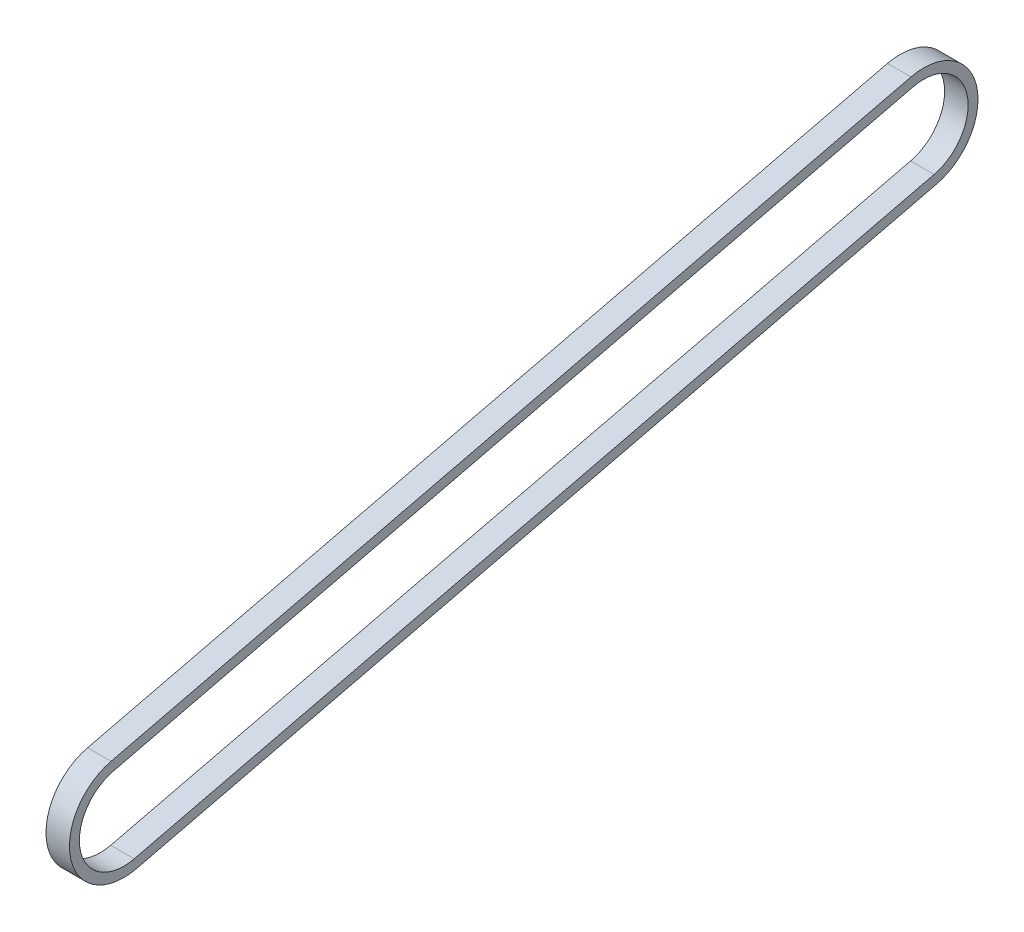
SolidWorks part; units mm, degrees
material "Caucho de silicio"
ref_plane "Alzado" through (0, 0, 0) normal (0, 0, 1) x (1, 0, 0)
ref_plane "Planta" through (0, 0, 0) normal (0, 1, 0) x (1, 0, 0)
ref_plane "Vista lateral" through (0, 0, 0) normal (1, 0, 0) x (0, 0, -1)
sketch "Croquis1" plane through (0, 0, 0) normal (0, 1, 0) x (1, 0, 0)
  line L1 (-101.6, -12.7) -> (101.6, -12.7)
  line L2 (-101.6, -12.7) -> (-101.6, 12.7)
  line L3 (-101.6, 12.7) -> (101.6, 12.7)
  line L4 (101.6, -12.7) -> (101.6, 12.7)
  line L5 (-101.6, -12.7) -> (101.6, 12.7) construction
  line L6 (-101.6, 12.7) -> (101.6, -12.7) construction
  point P0 (0, 0)
  dimension "D1" = 25.4
  dimension "D2" = 203.2
extrude "Saliente-Extruir1" add sketch "Croquis1" along normal blind 25.4
shell "Vaciado1" thickness 3.175 removed face at (-101.6, 12.7, 0) removed face at (101.6, 12.7, 0)
sketch "Croquis2" plane through (0, 25.4, 0) normal (0, 1, 0) x (1, 0, 0)
  line L0 (101.6, 12.7) -> (-101.6, 12.7) construction
  line L1 (-25.4, -12.7) -> (25.4, -12.7)
  line L2 (-25.4, -12.7) -> (-25.4, 12.7)
  line L3 (-25.4, 12.7) -> (25.4, 12.7)
  line L4 (25.4, -12.7) -> (25.4, 12.7)
  line L5 (-25.4, -12.7) -> (25.4, 12.7) construction
  line L6 (-25.4, 12.7) -> (25.4, -12.7) construction
  line L8 (-22.225, -9.525) -> (22.225, -9.525)
  line L9 (-22.225, -9.525) -> (-22.225, 9.525)
  line L10 (-22.225, 9.525) -> (22.225, 9.525)
  line L11 (22.225, -9.525) -> (22.225, 9.525)
  line L12 (-22.225, -9.525) -> (22.225, 9.525) construction
  line L13 (-22.225, 9.525) -> (22.225, -9.525) construction
  point P0 (0, 0)
  point P8 (0, 0)
  dimension "D1" = 50.8
  dimension "D2" = 3.175
  dimension "D3" = 3.175
extrude "Saliente-Extruir2" add sketch "Croquis2" along normal blind 247.65 separate body
sketch "Croquis3" plane through (0, 25.4, 0) normal (0, 1, 0) x (1, 0, 0)
  line L0 (0, 0) -> (0, 12.7) construction
  line L1 (25.4, 12.7) -> (-25.4, 12.7) construction
  circle A0 centre (-47.625, 0) radius 3.2639
  circle A1 centre (-79.375, 0) radius 3.2639
  circle A2 centre (79.375, 0) radius 3.2639
  circle A3 centre (47.625, 0) radius 3.2639
  dimension "D1" = 47.625
  dimension "D2" = 6.5278
  dimension "D3" = 31.75
extrude "Cortar-Extruir1" cut sketch "Croquis3" against normal through all
sketch "Croquis4" plane through (0, 0, 12.7) normal (0, 0, 1) x (1, 0, 0)
  line L0 (0, 25.4) -> (0, 139.6619) construction
  line L1 (-101.6, 25.4) -> (101.6, 25.4) construction
  line L2 (0, 139.6619) -> (-23.8125, 139.6619) construction
  circle A0 centre (0, 139.6619) radius 14.3129
  circle A1 centre (0, 139.6619) radius 23.8125 construction
  circle A2 centre (-23.8125, 139.6619) radius 2.4892 construction
  circle A3 centre (-11.9062, 160.2841) radius 2.4892
  circle A4 centre (11.9063, 160.2841) radius 2.4892
  circle A5 centre (23.8125, 139.6619) radius 2.4892 construction
  circle A6 centre (11.9062, 119.0397) radius 2.4892
  circle A7 centre (-11.9063, 119.0397) radius 2.4892
  dimension "D1" = 28.6258
  dimension "D3" = 47.625
  dimension "D4" = 4.9784
  dimension "D2" = 114.2619
  dimension "D6" = 23.8125
  dimension "D5" = 6
extrude "Cortar-Extruir2" cut sketch "Croquis4" against normal through all
sketch "Croquis8" plane through (0, 0, 12.7) normal (0, 0, 1) x (1, 0, 0)
  line L0 (0, 0) -> (0, 273.05) construction
  line L1 (-101.6, 12.7) -> (0, 12.7) construction
  line L2 (-101.6, 25.4) -> (-101.6, 0) construction
  line L3 (0, 12.7) -> (-12.7, 12.7) construction
  line L4 (0, 12.7) -> (12.7, 12.7) construction
  line L5 (-25.4, 273.05) -> (25.4, 273.05) construction
  line L6 (-12.7, 12.7) -> (-12.7, 25.4) construction
  circle A0 centre (0, 12.7) radius 2.4892
  circle A1 centre (-12.7, 12.7) radius 2.4892
  circle A2 centre (-25.4, 12.7) radius 2.4892
  circle A3 centre (-38.1, 12.7) radius 2.4892
  circle A4 centre (-50.8, 12.7) radius 2.4892
  circle A5 centre (0, 12.7) radius 2.4892
  circle A6 centre (-12.7, 12.7) radius 2.4892
  circle A7 centre (-25.4, 12.7) radius 2.4892
  circle A8 centre (-38.1, 12.7) radius 2.4892
  circle A9 centre (12.7, 12.7) radius 2.4892
  circle A10 centre (0, 12.7) radius 2.4892
  circle A11 centre (-12.7, 12.7) radius 2.4892
  circle A12 centre (-25.4, 12.7) radius 2.4892
  circle A13 centre (25.4, 12.7) radius 2.4892
  circle A14 centre (12.7, 12.7) radius 2.4892
  circle A15 centre (0, 12.7) radius 2.4892
  circle A16 centre (-12.7, 12.7) radius 2.4892
  circle A17 centre (38.1, 12.7) radius 2.4892
  circle A18 centre (25.4, 12.7) radius 2.4892
  circle A19 centre (12.7, 12.7) radius 2.4892
  circle A20 centre (0, 12.7) radius 2.4892
  circle A21 centre (12.7, 12.7) radius 2.4892
  circle A22 centre (25.4, 12.7) radius 2.4892
  circle A23 centre (38.1, 12.7) radius 2.4892
  circle A24 centre (50.8, 12.7) radius 2.4892
  circle A25 centre (-12.7, 25.4) radius 2.4892 [skipped]
  circle A26 centre (12.7, 25.4) radius 2.4892 [skipped]
  circle A27 centre (-12.7, 38.1) radius 2.4892
  circle A28 centre (12.7, 38.1) radius 2.4892
  circle A29 centre (-12.7, 50.8) radius 2.4892
  circle A30 centre (12.7, 50.8) radius 2.4892
  circle A31 centre (-12.7, 63.5) radius 2.4892
  circle A32 centre (12.7, 63.5) radius 2.4892
  circle A33 centre (-12.7, 76.2) radius 2.4892
  circle A34 centre (12.7, 76.2) radius 2.4892
  dimension "D1" = 4.9784
  dimension "D4" = 12.7
  dimension "D5" = 12.7
  dimension "D7" = 12.7
  dimension "D2" = 5
  dimension "D3" = 5
  dimension "D6" = 6
extrude "Cortar-Extruir4" cut sketch "Croquis8" against normal through all contours A4 | A3 | A2 | A1 | A0 | A9 | A13 | A17 | A24 | A28 | A29 | A30 | A31 | A32 | A34 | A33 | A27 region at (0, 12.7, 12.7) region at (-12.7, 12.7, 12.7) region at (-25.4, 12.7, 12.7) region at (-38.1, 12.7, 12.7) region at (-50.8, 12.7, 12.7) region at (12.7, 12.7, 12.7) region at (25.4, 12.7, 12.7) region at (38.1, 12.7, 12.7) region at (50.8, 12.7, 12.7) region at (12.7, 38.1, 12.7) region at (-12.7, 50.8, 12.7) region at (12.7, 50.8, 12.7) region at (-12.7, 63.5, 12.7) region at (12.7, 63.5, 12.7) region at (-12.7, 76.2, 12.7) region at (12.7, 76.2, 12.7)
sketch "Croquis6" plane through (0, 0, 12.7) normal (0, 0, 1) x (1, 0, 0)
  line L0 (25.4, 273.05) -> (25.4, 25.4) construction
  line L1 (-25.4, 88.646) -> (25.4, 88.646)
  line L2 (-25.4, 88.646) -> (-25.4, 114.046)
  line L3 (-25.4, 114.046) -> (25.4, 114.046)
  line L4 (25.4, 88.646) -> (25.4, 114.046)
  line L5 (-25.4, 88.646) -> (25.4, 114.046) construction
  line L6 (-25.4, 114.046) -> (25.4, 88.646) construction
  line L7 (-101.6, 25.4) -> (101.6, 25.4) construction
  line L9 (-22.225, 91.821) -> (22.225, 91.821)
  line L10 (-22.225, 91.821) -> (-22.225, 110.871)
  line L11 (-22.225, 110.871) -> (22.225, 110.871)
  line L12 (22.225, 91.821) -> (22.225, 110.871)
  line L13 (-22.225, 91.821) -> (22.225, 110.871) construction
  line L14 (-22.225, 110.871) -> (22.225, 91.821) construction
  point P0 (0, 101.346)
  point P11 (0, 101.346)
  dimension "D1" = 25.4
  dimension "D2" = 63.246
  dimension "D3" = 3.175
  dimension "D4" = 3.175
extrude "Saliente-Extruir3" add sketch "Croquis6" along normal blind 69.85 separate body
sketch "Croquis7" plane through (0, 114.046, 0) normal (0, 1, 0) x (1, 0, 0)
  line L0 (0, -12.7) -> (0, -82.55) construction
  line L1 (-25.4, -12.7) -> (25.4, -12.7) construction
  line L2 (25.4, -82.55) -> (-25.4, -82.55) construction
  line L3 (16.51, -12.7) -> (-16.51, -12.7)
  line L4 (25.4, -12.7) -> (-25.4, -12.7) construction
  line L5 (-16.51, -12.7) -> (-16.51, -34.798)
  line L6 (-13.208, -38.1) -> (13.208, -38.1)
  line L7 (16.51, -12.7) -> (16.51, -34.798)
  arc A0 (16.51, -34.798) -> (13.208, -38.1) centre (13.208, -34.798) cw
  arc A1 (-16.51, -34.798) -> (-13.208, -38.1) centre (-13.208, -34.798) ccw
  point P12 (0, -38.1)
  point P16 (16.51, -38.1)
  point P19 (-16.51, -38.1)
  dimension "D3" = 3.302
  dimension "D1" = 25.4
  dimension "D2" = 33.02
extrude "Cortar-Extruir3" cut sketch "Croquis7" against normal up to next (3.175 mm away)
sketch "Croquis11" plane through (25.4, 0, 0) normal (1, 0, 0) x (0, 0, -1)
  line L0 (0, -101.854) -> (-381, -101.854) construction
  line L1 (-82.55, 88.646) -> (-82.55, 114.046) construction
  line L2 (-82.55, 88.646) -> (-12.7, 88.646) construction
  line L6 (-517.96, -101.854) -> (-276.66, -101.854) construction
  line L7 (-517.96, -101.854) -> (-517.96, 139.446) construction
  line L8 (-517.96, 139.446) -> (-276.66, 139.446) construction
  line L9 (-276.66, -101.854) -> (-276.66, 139.446) construction
  circle A0 centre (-396.875, 145.796) radius 38.1
  dimension "D3" = 76.2
  dimension "D4" = 209.55
  dimension "D5" = 276.225
  dimension "D1" = 190.5
  dimension "D2" = 381
  dimension "D6" = 241.3
sketch "Croquis9" plane through (0, 0, 12.7) normal (0, 0, 1) x (1, 0, 0)
  line L0 (0, 0) -> (0, 273.05) construction
  line L1 (-25.4, 273.05) -> (25.4, 273.05) construction
  line L2 (50.8, 0) -> (-50.8, 0)
  line L3 (-101.6, 0) -> (101.6, 0) construction
  line L4 (-57.15, 6.35) -> (-57.15, 23.7481)
  line L5 (-101.6, 25.4) -> (101.6, 25.4) construction
  line L6 (-56.3451, 26.8425) -> (-27.2168, 79.0403)
  line L7 (-25.4, 273.05) -> (-25.4, 25.4) construction
  line L8 (-21.6717, 82.296) -> (21.6717, 82.296)
  line L9 (56.3451, 26.8425) -> (27.2168, 79.0403)
  line L10 (57.15, 6.35) -> (57.15, 23.7481)
  line L11 (-25.4, 88.646) -> (25.4, 88.646) construction
  circle A0 centre (-50.8, 12.7) radius 2.4892 construction
  arc A2 (-50.8, 0) -> (-57.15, 6.35) centre (-50.8, 6.35) cw
  arc A3 (-57.15, 23.7481) -> (-56.3451, 26.8425) centre (-50.8, 23.7481) cw
  arc A4 (-27.2168, 79.0403) -> (-21.6717, 82.296) centre (-21.6717, 75.946) cw
  arc A5 (27.2168, 79.0403) -> (21.6717, 82.296) centre (21.6717, 75.946) ccw
  arc A6 (57.15, 23.7481) -> (56.3451, 26.8425) centre (50.8, 23.7481) ccw
  arc A7 (50.8, 0) -> (57.15, 6.35) centre (50.8, 6.35) ccw
  circle A9 centre (-25.4, 12.7) radius 2.4892
  circle A10 centre (-25.4, 12.7) radius 2.4892
  circle A11 centre (-12.7, 12.7) radius 2.4892
  circle A12 centre (-12.7, 12.7) radius 2.4892
  circle A13 centre (0, 12.7) radius 2.4892
  circle A14 centre (0, 12.7) radius 2.4892
  circle A15 centre (0, 12.7) radius 2.4892
  circle A16 centre (0, 12.7) radius 2.4892
  circle A17 centre (12.7, 12.7) radius 2.4892
  circle A18 centre (12.7, 12.7) radius 2.4892
  circle A19 centre (-38.1, 12.7) radius 2.4892
  circle A20 centre (-38.1, 12.7) radius 2.4892
  circle A21 centre (-25.4, 12.7) radius 2.4892
  circle A22 centre (-25.4, 12.7) radius 2.4892
  circle A23 centre (-12.7, 12.7) radius 2.4892
  circle A24 centre (-12.7, 12.7) radius 2.4892
  circle A25 centre (0, 12.7) radius 2.4892
  circle A26 centre (0, 12.7) radius 2.4892
  circle A27 centre (-50.8, 12.7) radius 2.4892
  circle A28 centre (-50.8, 12.7) radius 2.4892
  circle A29 centre (-38.1, 12.7) radius 2.4892
  circle A30 centre (-38.1, 12.7) radius 2.4892
  circle A31 centre (25.4, 12.7) radius 2.4892
  circle A32 centre (25.4, 12.7) radius 2.4892
  circle A33 centre (38.1, 12.7) radius 2.4892
  circle A34 centre (38.1, 12.7) radius 2.4892
  circle A35 centre (-12.7, 12.7) radius 2.4892
  circle A36 centre (-12.7, 12.7) radius 2.4892
  circle A37 centre (0, 12.7) radius 2.4892
  circle A38 centre (0, 12.7) radius 2.4892
  circle A39 centre (12.7, 12.7) radius 2.4892
  circle A40 centre (12.7, 12.7) radius 2.4892
  circle A41 centre (25.4, 12.7) radius 2.4892
  circle A42 centre (25.4, 12.7) radius 2.4892
  circle A43 centre (-25.4, 12.7) radius 2.4892
  circle A44 centre (-25.4, 12.7) radius 2.4892
  circle A45 centre (-12.7, 12.7) radius 2.4892
  circle A46 centre (-12.7, 12.7) radius 2.4892
  circle A47 centre (50.8, 12.7) radius 2.4892
  circle A48 centre (50.8, 12.7) radius 2.4892
  circle A49 centre (38.1, 12.7) radius 2.4892
  circle A50 centre (38.1, 12.7) radius 2.4892
  circle A51 centre (25.4, 12.7) radius 2.4892
  circle A52 centre (25.4, 12.7) radius 2.4892
  circle A53 centre (12.7, 12.7) radius 2.4892
  circle A54 centre (12.7, 12.7) radius 2.4892
  circle A55 centre (0, 12.7) radius 2.4892
  circle A56 centre (0, 12.7) radius 2.4892
  circle A57 centre (12.7, 12.7) radius 2.4892
  circle A58 centre (12.7, 12.7) radius 2.4892
  circle A59 centre (-12.7, 76.2) radius 2.4892
  circle A60 centre (-12.7, 76.2) radius 2.4892
  circle A61 centre (12.7, 63.5) radius 2.4892
  circle A62 centre (12.7, 63.5) radius 2.4892
  circle A63 centre (-12.7, 63.5) radius 2.4892
  circle A64 centre (-12.7, 63.5) radius 2.4892
  circle A65 centre (12.7, 50.8) radius 2.4892
  circle A66 centre (12.7, 50.8) radius 2.4892
  circle A67 centre (-12.7, 50.8) radius 2.4892
  circle A68 centre (-12.7, 50.8) radius 2.4892
  circle A69 centre (12.7, 38.1) radius 2.4892
  circle A70 centre (12.7, 38.1) radius 2.4892
  circle A71 centre (-12.7, 38.1) radius 2.4892
  circle A72 centre (-12.7, 38.1) radius 2.4892
  circle A73 centre (12.7, 76.2) radius 2.4892
  circle A74 centre (12.7, 76.2) radius 2.4892
  point P22 (-57.15, 0)
  point P25 (-57.15, 25.4)
  point P28 (-25.4, 82.296)
  point P38 (0, 82.296)
  dimension "D1" = 6.35
  dimension "D3" = 6.35
  dimension "D37" = 6.35
  dimension "D4" = 0
  dimension "D5" = 0
  dimension "D6" = 0
  dimension "D7" = 0
  dimension "D8" = 0
  dimension "D9" = 0
  dimension "D10" = 0
  dimension "D11" = 0
  dimension "D12" = 0
  dimension "D13" = 0
  dimension "D14" = 0
  dimension "D15" = 0
  dimension "D16" = 0
  dimension "D17" = 0
  dimension "D18" = 0
  dimension "D19" = 0
  dimension "D20" = 0
  dimension "D21" = 0
  dimension "D22" = 0
  dimension "D23" = 0
  dimension "D24" = 0
  dimension "D25" = 0
  dimension "D26" = 0
  dimension "D27" = 0
  dimension "D28" = 0
  dimension "D29" = 0
  dimension "D30" = 0
  dimension "D31" = 0
  dimension "D32" = 0
  dimension "D33" = 0
  dimension "D34" = 0
  dimension "D35" = 0
  dimension "D36" = 0
extrude "Saliente-Extruir4" add sketch "Croquis9" along normal blind 6.35 separate body contours L0 L8 A4 L6 A3 A60 A64 A68 A72 | L0 A6 L9 A5 L8 A74 A70 A66 A62 | L0 A3 L4 A2 | L0 L2 A7 L10 A6 A56 region at (-24.3725, 36.0328, 12.7) region at (24.3725, 36.0328, 12.7)
sketch "Croquis15" plane through (25.4, 0, 0) normal (1, 0, 0) x (0, 0, -1)
  line L0 (-12.7, 0) -> (-12.7, 171.1325) construction
  line L1 (-12.7, 273.05) -> (-12.7, 25.4) construction
  line L2 (-72.5746, 227.1642) -> (-41.5317, 154.1315) construction
  line L3 (-105.4538, 208.2656) -> (-57.9713, 144.6822) construction
  line L4 (-94.6246, 238.2605) -> (-401.3483, 164.3633) construction
  line L5 (-392.4017, 127.2287) -> (-85.6779, 201.1258) construction
  line L8 (-82.55, 114.046) -> (-12.7, 114.046) construction
  circle A0 centre (-50.32, 150.396) radius 30
  arc A1 (-57.9713, 144.6822) -> (-41.5317, 154.1315) centre (-50.32, 150.396) ccw construction
  arc A2 (-401.3483, 164.3633) -> (-392.4017, 127.2287) centre (-396.875, 145.796) ccw construction
  arc A3 (-72.5746, 227.1642) -> (-105.4538, 208.2656) centre (-90.1513, 219.6932) ccw construction
  arc A4 (-85.6779, 201.1258) -> (-94.6246, 238.2605) centre (-90.1513, 219.6932) ccw construction
  dimension "D2" = 60
  dimension "D3" = 19.0986
  dimension "D4" = 38.1972
  dimension "D1" = 171.1325
  dimension "D7" = 6.35
  dimension "D8" = 7.62
sketch "Croquis16" plane through (25.4, 0, 0) normal (1, 0, 0) x (0, 0, -1)
  line L0 (-50.32, 150.396) -> (-50.32, 175.796) construction
  line L1 (-13.329, 272.9215) -> (-117.7691, 251.586)
  line L2 (-82.55, 94.996) -> (-82.55, 113.9625)
  line L3 (-82.5522, 114.1295) -> (-83.4835, 149.5234)
  line L4 (-76.2, 88.646) -> (6.35, 88.646)
  line L5 (12.7, 273.05) -> (12.7, 25.4) construction
  line L6 (12.7, 94.996) -> (12.7, 266.7)
  line L7 (6.35, 273.05) -> (-12.058, 273.05)
  line L9 (-122.7196, 244.0935) -> (-110.5184, 184.367)
  line L10 (-94.6246, 238.2605) -> (-401.3483, 164.3633) construction
  circle A0 centre (-90.1513, 219.6932) radius 14.3256
  circle A1 centre (-50.32, 150.396) radius 33.175
  circle A4 centre (-50.32, 150.396) radius 9.5631
  circle A5 centre (-50.32, 150.396) radius 25.4 construction
  circle A6 centre (-50.32, 175.796) radius 2.4892
  circle A7 centre (-32.3595, 168.3565) radius 2.4892 construction
  circle A8 centre (-24.92, 150.396) radius 2.4892
  circle A9 centre (-32.3595, 132.4355) radius 2.4892
  circle A10 centre (-50.32, 124.996) radius 2.4892
  circle A11 centre (-68.2805, 132.4355) radius 2.4892
  circle A12 centre (-75.72, 150.396) radius 2.4892
  circle A13 centre (-68.2805, 168.3565) radius 2.4892
  arc A18 (-105.4068, 178.645) -> (-83.4801, 149.4007) centre (-115.2158, 148.4482) cw
  arc A19 (-110.5184, 184.367) -> (-105.4068, 178.645) centre (-103.0526, 185.8922) ccw
  arc A21 (-117.7691, 251.586) -> (-122.7196, 244.0935) centre (-116.4981, 245.3645) ccw
  arc A23 (-12.058, 273.05) -> (-13.329, 272.9215) centre (-12.058, 266.7) ccw
  circle A26 centre (-50.32, 150.396) radius 30 construction
  arc A29 (-82.55, 113.9625) -> (-82.5522, 114.1295) centre (-88.9, 113.9625) ccw
  arc A31 (12.7, 266.7) -> (6.35, 273.05) centre (6.35, 266.7) ccw
  arc A32 (6.35, 88.646) -> (12.7, 94.996) centre (6.35, 94.996) ccw
  arc A33 (-82.55, 94.996) -> (-76.2, 88.646) centre (-76.2, 94.996) ccw
  point P45 (-12.7, 273.05)
  point P72 (-82.55, 114.046)
  point P74 (12.7, 273.05)
  point P77 (12.7, 88.646)
  point P80 (-82.55, 88.646)
  dimension "D1" = 28.6512
  dimension "D2" = 3.175
  dimension "D3" = 31.75
  dimension "D4" = 19.1262
  dimension "D5" = 50.8
  dimension "D6" = 4.9784
  dimension "D9" = 7.62
  dimension "D10" = 6.35
  dimension "D13" = 60.96
  dimension "D14" = 6.35
  dimension "D15" = 6.35
  dimension "D12" = 6.35
  dimension "D8" = 25.4
  dimension "D11" = 12.7
  dimension "D16" = 2
  dimension "D7" = 8
extrude "Saliente-Extruir5" add sketch "Croquis16" along normal blind 6.35 separate body contours L4 A32 A31 A23 | L2 A33 L4 A23 L1 A21 L9 A19 A18 A1 L3 A29 A0 | A1 A13 A12 A11 A10 A9 A8 A6 A4 region at (25.4, 189.4289, 39.9715) region at (25.4, 182.6299, 50.744)
sketch "Croquis12" plane through (25.4, 0, 0) normal (1, 0, 0) x (0, 0, -1)
  line L0 (-82.55, 101.346) -> (-12.7, 101.346) construction
  line L1 (-82.55, 88.646) -> (-82.55, 114.046) construction
  line L2 (-12.7, 88.646) -> (-12.7, 114.046) construction
  line L3 (0, 273.05) -> (0, 0) construction
  line L4 (-12.7, 273.05) -> (12.7, 273.05) construction
  line L5 (0, 101.346) -> (-12.7, 101.346) construction
  line L6 (0, 101.346) -> (0, 114.046) construction
  circle A1 centre (0, 101.346) radius 2.4892
  circle A2 centre (-12.7, 101.346) radius 2.4892 [skipped]
  circle A3 centre (-25.4, 101.346) radius 2.4892
  circle A4 centre (-38.1, 101.346) radius 2.4892
  circle A5 centre (-50.8, 101.346) radius 2.4892
  circle A6 centre (0, 114.046) radius 2.4892
  circle A7 centre (0, 126.746) radius 2.4892
  circle A8 centre (0, 139.446) radius 2.4892
  circle A9 centre (0, 152.146) radius 2.4892
  circle A10 centre (0, 164.846) radius 2.4892
  circle A11 centre (0, 177.546) radius 2.4892
  circle A12 centre (0, 190.246) radius 2.4892
  circle A13 centre (0, 202.946) radius 2.4892
  circle A14 centre (0, 215.646) radius 2.4892
  circle A15 centre (0, 228.346) radius 2.4892
  circle A16 centre (0, 241.046) radius 2.4892
  circle A17 centre (0, 253.746) radius 2.4892
  circle A18 centre (0, 266.446) radius 2.4892
  circle A19 centre (-63.5, 101.346) radius 2.4892
  circle A20 centre (-76.2, 101.346) radius 2.4892
  dimension "D1" = 4.9784
  dimension "D3" = 12.7
  dimension "D5" = 12.7
  dimension "D2" = 7
  dimension "D4" = 14
extrude "Cortar-Extruir5" cut sketch "Croquis12" against normal through all and the other way through all
sketch "Croquis17" plane through (31.75, 0, 0) normal (1, 0, 0) x (0, 0, -1)
  line L0 (-403.8236, 170.2271) -> (-118.0462, 251.5072)
  line L1 (-117.4868, 251.6437) -> (-21.8452, 271.1818)
  line L3 (-122.7196, 244.0935) -> (-110.5184, 184.367) construction
  line L4 (-12.7, 273.05) -> (-12.7, 25.4) construction
  line L5 (-12.7, 206.2243) -> (-12.7, 263.716)
  line L6 (-411.78, 166.363) -> (-373.2477, 194.2875)
  line L8 (-136.7418, 185.5575) -> (-321.1054, 141.1398)
  line L9 (-13.329, 272.9215) -> (-117.7691, 251.586) construction
  line L10 (-392.4017, 127.2287) -> (-85.6779, 201.1258) construction
  line L11 (-321.1054, 141.1398) -> (-371.9054, 141.1398)
  circle A0 centre (-396.875, 145.796) radius 14.3256
  circle A1 centre (-90.1513, 219.6932) radius 14.3256
  circle A2 centre (-396.875, 145.796) radius 25.4
  arc A3 (-118.0462, 251.5072) -> (-117.4868, 251.6437) centre (-115.9616, 244.1779) cw
  arc A4 (-21.8452, 271.1818) -> (-12.7, 263.716) centre (-20.32, 263.716) cw
  arc A5 (-12.7, 206.2243) -> (-43.5311, 181.4117) centre (-38.1, 206.2243) cw
  circle A6 centre (-50.32, 150.396) radius 31.75
  arc A10 (-368.4979, 195.7323) -> (-273.9823, 207.1562) centre (-357.3657, 500.3289) ccw
  arc A13 (-90.6096, 168.5131) -> (-75.8725, 169.2409) centre (-83.5383, 174.8944) ccw
  circle A15 centre (-368.7762, 188.1174) radius 7.62
  circle A17 centre (-116.2498, 180.6969) radius 6.35
  circle A18 centre (-396.875, 145.796) radius 38.1 construction
  circle A19 centre (-368.7762, 188.1174) radius 6.35 construction
  arc A20 (-83.4801, 149.4007) -> (-105.4068, 178.645) centre (-115.2158, 148.4482) ccw construction
  arc A24 (-90.6096, 168.5131) -> (-114.2186, 174.6806) centre (-107.1094, 153.6233) ccw
  arc A25 (-136.7418, 185.5575) -> (-122.089, 178.2015) centre (-133.7672, 173.2107) cw
  circle A26 centre (-103.445, 184.6843) radius 6.35
  arc A28 (-110.5184, 184.367) -> (-105.4068, 178.645) centre (-103.0526, 185.8922) ccw construction
  arc A30 (-83.484, 149.5233) -> (-105.4068, 178.645) centre (-115.2158, 148.4482) ccw construction
  point P19 (-117.7691, 251.586)
  dimension "D1" = 28.6512
  dimension "D2" = 50.8
  dimension "D3" = 7.62
  dimension "D4" = 63.5
  dimension "D5" = 9.525
  dimension "D6" = 25.4
  dimension "D7" = 50.8
  dimension "D8" = 12.7
  dimension "D9" = 15.24
  dimension "D10" = 12.7
  dimension "D11" = 304.8
  dimension "D12" = 76.2
  dimension "D13" = 12.7
  dimension "D16" = 12.7
  dimension "D17" = 12.7
  dimension "D18" = 22.225
  dimension "D14" = 3.175
  dimension "D15" = 50.8
extrude "Saliente-Extruir6" add sketch "Croquis17" along normal blind 6.35 separate body contours A2 L0 | L5 A4 A3 L0 | A2 A0 | A2 L0 | A15 | A15 L0 | A17 | A26 region at (31.75, 200.7242, 175.8834) region at (31.75, 192.4732, 340.2276) region at (31.75, 179.8601, 385.7751) region at (31.75, 188.1174, 368.7762) region at (31.75, 165.4916, 382.0001) region at (31.75, 180.6969, 116.2498) region at (31.75, 184.6843, 103.445)
sketch "Croquis18" plane through (38.1, 0, 0) normal (1, 0, 0) x (0, 0, -1)
  line L0 (-122.7196, 244.0935) -> (-110.5184, 184.367) construction
  line L1 (-122.5235, 243.1334) -> (-110.0283, 181.9679)
  line L2 (-403.8236, 170.2271) -> (-118.0462, 251.5072) construction
  line L5 (-411.78, 166.363) -> (-373.2477, 194.2875) construction
  line L7 (-403.8236, 170.2271) -> (-130.4821, 247.9702)
  line L8 (-411.78, 166.363) -> (-373.2477, 194.2875)
  line L9 (-136.7418, 185.5575) -> (-321.1054, 141.1398) construction
  line L12 (-321.1054, 141.1398) -> (-371.9054, 141.1398) construction
  line L13 (-321.1054, 141.1398) -> (-371.9054, 141.1398)
  line L14 (-136.7418, 185.5575) -> (-321.1054, 141.1398)
  circle A1 centre (-396.875, 145.796) radius 25.4
  circle A2 centre (-396.875, 145.796) radius 25.4
  circle A5 centre (-396.875, 145.796) radius 14.3256
  circle A6 centre (-396.875, 145.796) radius 14.3256
  arc A12 (-122.5235, 243.1334) -> (-130.4821, 247.9702) centre (-128.745, 241.8624) ccw
  arc A13 (-368.4979, 195.7323) -> (-273.9823, 207.1562) centre (-357.3657, 500.3289) ccw construction
  arc A14 (-122.089, 178.2015) -> (-114.2186, 174.6806) centre (-116.2498, 180.6969) ccw construction
  arc A15 (-122.089, 178.2015) -> (-136.7418, 185.5575) centre (-133.7672, 173.2107) ccw construction
  arc A17 (-368.4979, 195.7323) -> (-373.2477, 194.2875) centre (-368.7762, 188.1174) ccw construction
  arc A18 (-368.4979, 195.7323) -> (-273.9823, 207.1562) centre (-357.3657, 500.3289) ccw
  arc A19 (-368.4979, 195.7323) -> (-373.2477, 194.2875) centre (-368.7762, 188.1174) ccw
  arc A20 (-122.089, 178.2015) -> (-114.2186, 174.6806) centre (-116.2498, 180.6969) ccw
  arc A21 (-122.089, 178.2015) -> (-136.7418, 185.5575) centre (-133.7672, 173.2107) ccw
  circle A22 centre (-116.2498, 180.6969) radius 6.35
  dimension "D2" = 6.35
  dimension "D1" = 0
  dimension "D3" = 0
extrude "Saliente-Extruir7" add sketch "Croquis18" along normal blind 6.35 from surface separate body contours L1 A12 A2 | A2 | A2 L7 | A22 region at (38.1, 189.052, 239.9072) region at (38.1, 180.6969, 116.2498) region at (38.1, 187.7771, 359.9808) region at (38.1, 165.4916, 382.0001) starting at face at (25.4, 101.346, -2.4892)
sketch "Croquis22" plane through (38.1, 0, 0) normal (1, 0, 0) x (0, 0, -1)
  line L0 (-396.875, 145.796) -> (-90.1513, 219.6932) construction
  line L1 (-90.1513, 219.6932) -> (-50.32, 150.396) construction
  line L4 (-273.9823, 207.1562) -> (-118.0462, 251.5072) construction
  line L5 (-21.8452, 271.1818) -> (-117.4868, 251.6437) construction
  line L6 (-122.7196, 244.0935) -> (-110.5184, 184.367) construction
  circle A1 centre (-347.4881, 157.6945) radius 3.2639
  circle A2 centre (-396.875, 145.796) radius 19.0986 construction
  arc A3 (-401.3483, 164.3633) -> (-392.4017, 127.2287) centre (-396.875, 145.796) ccw construction
  circle A4 centre (-347.4881, 157.6945) radius 6.35 construction
  circle A7 centre (-72.747, 189.4137) radius 3.2639
  circle A8 centre (-72.747, 189.4137) radius 6.35 construction
  circle A9 centre (-50.32, 213.896) radius 6.35 construction
  circle A10 centre (-50.32, 213.896) radius 3.2639
  circle A15 centre (-72.747, 254.3022) radius 3.2639
  circle A16 centre (-72.747, 254.3022) radius 6.35 construction
  circle A17 centre (-20.32, 263.716) radius 6.35 construction
  circle A18 centre (-20.32, 263.716) radius 3.2639
  circle A19 centre (-368.7762, 188.1174) radius 3.2639
  circle A22 centre (-116.2498, 180.6969) radius 6.35 construction
  circle A23 centre (-116.2498, 180.6969) radius 3.2639
  circle A24 centre (-116.4981, 245.3645) radius 6.35 construction
  circle A25 centre (-116.4981, 245.3645) radius 3.2639
  arc A26 (-122.089, 178.2015) -> (-114.2186, 174.6806) centre (-116.2498, 180.6969) ccw construction
  circle A27 centre (-129.97, 241.514) radius 3.2639
  circle A28 centre (-129.97, 241.514) radius 6.35 construction
  circle A30 centre (-103.445, 184.6843) radius 6.35 construction
  circle A31 centre (-103.445, 184.6843) radius 3.2639
  arc A32 (-110.5184, 184.367) -> (-105.4068, 178.645) centre (-103.0526, 185.8922) ccw construction
  arc A33 (-83.4801, 149.4007) -> (-105.4068, 178.645) centre (-115.2158, 148.4482) ccw construction
  dimension "D1" = 6.5278
  dimension "D2" = 50.8
  dimension "D3" = 12.7
  dimension "D4" = 34.925
  dimension "D5" = 63.5
  dimension "D6" = 7.62
  dimension "D9" = 6.5278
extrude "Cortar-Extruir6" cut sketch "Croquis22" against normal through all
sketch "Croquis24" plane through (38.1, 0, 0) normal (1, 0, 0) x (0, 0, -1)
  line L0 (-396.875, 145.796) -> (-90.1513, 219.6932) construction
  line L1 (-243.5131, 182.7446) -> (-247.9864, 201.3119) construction
  line L2 (-94.6246, 238.2605) -> (-401.3483, 164.3633) construction
  circle A0 centre (-295.9867, 170.1024) radius 2.4892
  circle A1 centre (-191.0395, 195.3867) radius 2.4892
  circle A2 centre (-243.5131, 182.7446) radius 2.4892
  circle A3 centre (-147.826, 205.7979) radius 2.4892
  dimension "D1" = 4.9784
  dimension "D2" = 53.975
  dimension "D3" = 44.45
sketch "Croquis25" plane through (31.75, 0, 0) normal (1, 0, 0) x (0, 0, -1)
  line L0 (-12.7, 0) -> (-12.7, 139.7) construction
  line L1 (-12.7, 123.825) -> (-12.7, 155.575)
  line L2 (-12.7, 0) -> (-12.7, 171.1325) construction
  line L3 (-15.875, 158.75) -> (-17.145, 158.75)
  line L4 (-20.32, 155.575) -> (-20.32, 123.825)
  line L5 (-12.7, 139.7) -> (-20.32, 139.7) construction
  line L6 (-15.875, 120.65) -> (-17.145, 120.65)
  arc A0 (-12.7, 155.575) -> (-15.875, 158.75) centre (-15.875, 155.575) ccw
  arc A1 (-15.875, 120.65) -> (-12.7, 123.825) centre (-15.875, 123.825) ccw
  arc A2 (-17.145, 120.65) -> (-20.32, 123.825) centre (-17.145, 123.825) cw
  arc A3 (-17.145, 158.75) -> (-20.32, 155.575) centre (-17.145, 155.575) ccw
  point P13 (-12.7, 158.75)
  point P16 (-12.7, 120.65)
  point P19 (-20.32, 120.65)
  point P22 (-20.32, 158.75)
  dimension "D4" = 3.175
  dimension "D1" = 139.7
  dimension "D2" = 7.62
  dimension "D3" = 38.1
extrude "Cortar-Extruir8" cut sketch "Croquis25" against normal through all
extrude "Cortar-Extruir9" [suppressed] cut sketch "Croquis24" against normal through all
fillet "Redondeo1" [suppressed] radius 50.8
fillet "Redondeo2" [suppressed] radius 50.8
delete or keep bodies "Sólido-Eliminar/Conservar 1" [suppressed] type keep bodies bodies 112
delete or keep bodies "Sólido-Eliminar/Conservar 2" [suppressed] type keep bodies bodies 111
delete or keep bodies "Sólido-Eliminar/Conservar 3" [suppressed] type keep bodies bodies 107
delete or keep bodies "Sólido-Eliminar/Conservar 4" [suppressed] type keep bodies bodies 109
delete or keep bodies "Sólido-Eliminar/Conservar 5" [suppressed] type keep bodies bodies 121
delete or keep bodies "Sólido-Eliminar/Conservar 6" [suppressed] type keep bodies bodies 125
sketch "Croquis29" plane through (0, 0, 0) normal (1, 0, 0) x (0, 0, -1)
  line L0 (-392.4017, 127.2287) -> (-85.6779, 201.1258) construction
  line L1 (-94.6246, 238.2605) -> (-401.3483, 164.3633) construction
  line L2 (-392.4017, 127.2287) -> (-85.6779, 201.1258) construction
  line L3 (-94.6246, 238.2605) -> (-401.3483, 164.3633) construction
  line L4 (-392.8842, 129.2314) -> (-86.1604, 203.1285)
  line L5 (-94.1421, 236.2578) -> (-400.8658, 162.3606)
  line L6 (-391.9941, 125.5371) -> (-85.2704, 199.4342)
  line L7 (-95.0321, 239.9521) -> (-401.7559, 166.0549)
  arc A0 (-85.6779, 201.1258) -> (-94.6246, 238.2605) centre (-90.1513, 219.6932) ccw construction
  arc A1 (-401.3483, 164.3633) -> (-392.4017, 127.2287) centre (-396.875, 145.796) ccw construction
  arc A2 (-85.6779, 201.1258) -> (-94.6246, 238.2605) centre (-90.1513, 219.6932) ccw construction
  arc A3 (-401.3483, 164.3633) -> (-392.4017, 127.2287) centre (-396.875, 145.796) ccw construction
  arc A4 (-86.1604, 203.1285) -> (-94.1421, 236.2578) centre (-90.1513, 219.6932) ccw
  arc A5 (-400.8658, 162.3606) -> (-392.8842, 129.2314) centre (-396.875, 145.796) ccw
  arc A6 (-401.7559, 166.0549) -> (-391.9941, 125.5371) centre (-396.875, 145.796) ccw
  arc A7 (-85.2704, 199.4342) -> (-95.0321, 239.9521) centre (-90.1513, 219.6932) ccw
  dimension "D1" = 2.06
  dimension "D2" = 3.8
extrude "Saliente-Extruir9" add sketch "Croquis29" along normal mid plane 9 separate body
sketch "Croquis30" plane through (0, 0, 0) normal (1, 0, 0) x (0, 0, -1)
  line L0 (-72.5746, 227.1642) -> (-41.5317, 154.1315) construction
  line L1 (-105.4538, 208.2656) -> (-57.9713, 144.6822) construction
  line L2 (-72.5746, 227.1642) -> (-41.5317, 154.1315) construction
  line L3 (-105.4538, 208.2656) -> (-57.9713, 144.6822) construction
  line L4 (-74.4704, 226.3584) -> (-43.4275, 153.3257)
  line L5 (-103.8032, 209.4982) -> (-56.3207, 145.9148)
  line L6 (-106.8479, 207.2245) -> (-59.3654, 143.6411)
  line L7 (-70.9732, 227.8449) -> (-39.9303, 154.8122)
  arc A0 (-57.9713, 144.6822) -> (-41.5317, 154.1315) centre (-50.32, 150.396) ccw construction
  arc A1 (-72.5746, 227.1642) -> (-105.4538, 208.2656) centre (-90.1513, 219.6932) ccw construction
  arc A2 (-57.9713, 144.6822) -> (-41.5317, 154.1315) centre (-50.32, 150.396) ccw construction
  arc A3 (-72.5746, 227.1642) -> (-105.4538, 208.2656) centre (-90.1513, 219.6932) ccw construction
  arc A4 (-56.3207, 145.9148) -> (-43.4275, 153.3257) centre (-50.32, 150.396) ccw
  arc A5 (-74.4704, 226.3584) -> (-103.8032, 209.4982) centre (-90.1513, 219.6932) ccw
  arc A6 (-70.9732, 227.8449) -> (-106.8479, 207.2245) centre (-90.1513, 219.6932) ccw
  arc A7 (-59.3654, 143.6411) -> (-39.9303, 154.8122) centre (-50.32, 150.396) ccw
  dimension "D1" = 2.06
  dimension "D2" = 3.8
extrude "Saliente-Extruir10" add sketch "Croquis30" along normal mid plane 15 separate body
delete or keep bodies "Sólido-Eliminar/Conservar 7" type keep bodies bodies 123
delete or keep bodies "Sólido-Eliminar/Conservar 8" [suppressed] type keep bodies bodies 124
delete or keep bodies "Sólido-Eliminar/Conservar 9" [suppressed] type keep bodies bodies 126
delete or keep bodies "Sólido-Eliminar/Conservar 11" [suppressed] type keep bodies bodies 125
sketch "Croquis31" [suppressed] plane through (0, 0, -12.7) normal (0, 0, -1) x (-1, 0, 0)
  line L0 (0, 273.05) -> (0, 25.4) construction
  line L1 (-25.4, 273.05) -> (25.4, 273.05) construction
  line L2 (-25.4, 25.4) -> (25.4, 25.4) construction
  line L3 (-17.272, 238.125) -> (0, 238.125) construction
  line L4 (-17.272, 203.2) -> (17.272, 203.2) construction
  line L5 (-17.272, 203.2) -> (-17.272, 273.05) construction
  line L6 (-17.272, 273.05) -> (17.272, 273.05) construction
  line L7 (17.272, 203.2) -> (17.272, 273.05) construction
  line L8 (-17.272, 203.2) -> (17.272, 273.05) construction
  line L9 (-17.272, 273.05) -> (17.272, 203.2) construction
  line L10 (-18.8595, 257.683) -> (-18.8595, 262.763) construction
  line L11 (-20.447, 257.683) -> (-20.447, 262.763)
  line L12 (-17.272, 257.683) -> (-17.272, 262.763)
  line L13 (-18.8595, 218.567) -> (-18.8595, 213.487) construction
  line L14 (-20.447, 218.567) -> (-20.447, 213.487)
  line L15 (-17.272, 218.567) -> (-17.272, 213.487)
  line L16 (18.8595, 218.567) -> (18.8595, 213.487) construction
  line L17 (20.447, 218.567) -> (20.447, 213.487)
  line L18 (17.272, 218.567) -> (17.272, 213.487)
  line L19 (18.8595, 257.683) -> (18.8595, 262.763) construction
  line L20 (20.447, 257.683) -> (20.447, 262.763)
  line L21 (17.272, 257.683) -> (17.272, 262.763)
  arc A0 (-20.447, 257.683) -> (-17.272, 257.683) centre (-18.8595, 257.683) ccw
  arc A1 (-17.272, 262.763) -> (-20.447, 262.763) centre (-18.8595, 262.763) ccw
  arc A2 (-20.447, 218.567) -> (-17.272, 218.567) centre (-18.8595, 218.567) cw
  arc A3 (-17.272, 213.487) -> (-20.447, 213.487) centre (-18.8595, 213.487) cw
  arc A4 (20.447, 218.567) -> (17.272, 218.567) centre (18.8595, 218.567) ccw
  arc A5 (17.272, 213.487) -> (20.447, 213.487) centre (18.8595, 213.487) ccw
  arc A6 (20.447, 257.683) -> (17.272, 257.683) centre (18.8595, 257.683) cw
  arc A7 (17.272, 262.763) -> (20.447, 262.763) centre (18.8595, 262.763) cw
  point P6 (0, 238.125)
  point P13 (-18.8595, 260.223)
  point P22 (-18.8595, 216.027)
  point P29 (18.8595, 216.027)
  point P36 (18.8595, 260.223)
  dimension "D5" = 1.5875
  dimension "D1" = 69.85
  dimension "D2" = 34.544
  dimension "D3" = 22.098
  dimension "D4" = 5.08
extrude "Cortar-Extruir10" [suppressed] cut sketch "Croquis31" against normal up to next
equation "\"D1@Croquis15\"=5.5500+1.1875pulgadas"
equation "\"D3@Croquis15\"=(12*5mm)/pi"
equation "\"D4@Croquis15\"=(24*5mm)/pi"
equation "\"D5@Croquis15\"=(50*5mm)+1mm"
equation "\"D6@Croquis15\"=(150*5mm)+1mm"
